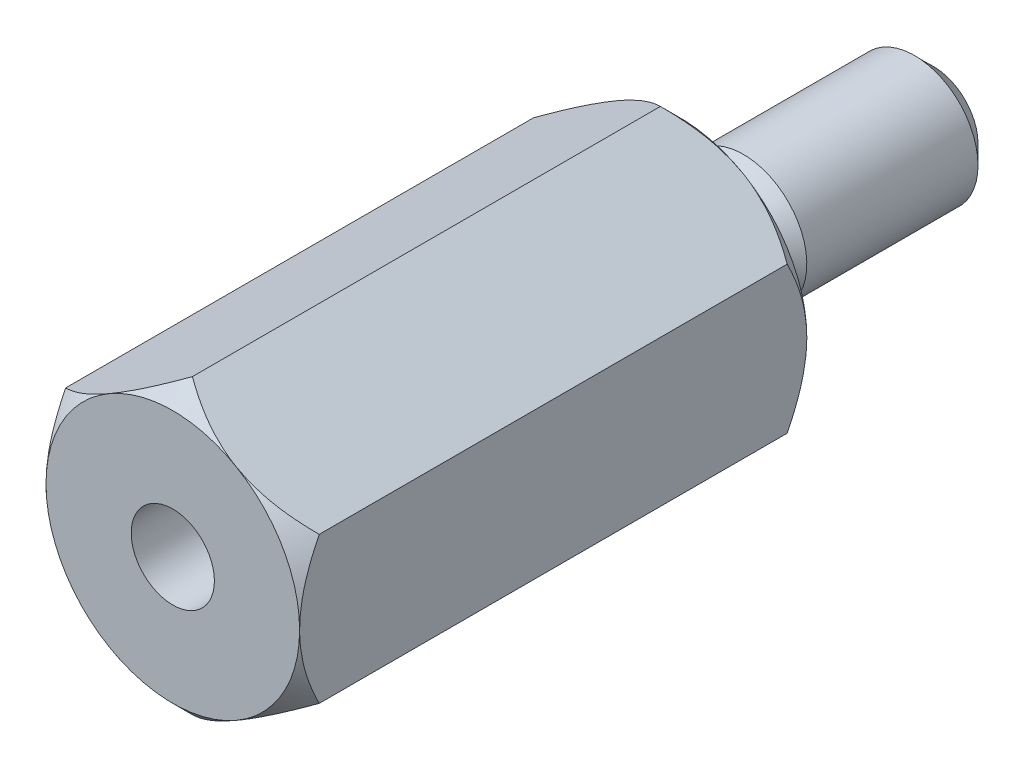
SolidWorks part; units mm, degrees
ref_plane "Front Plane" through (0, 0, 0) normal (0, 0, 1) x (1, 0, 0)
ref_plane "Top Plane" through (0, 0, 0) normal (0, 1, 0) x (1, 0, 0)
ref_plane "Right Plane" through (0, 0, 0) normal (1, 0, 0) x (0, 0, -1)
sketch "Sketch1" plane through (0, 0, 0) normal (1, 0, 0) x (0, 0, -1)
  line L0 (-19.05, 0) -> (19.05, 0) construction
  line L1 (19.05, 3.175) -> (19.05, -3.175) construction
  line L2 (-19.05, 2.0828) -> (-19.05, -2.0828) construction
  line L3 (19.05, 3.175) -> (17.78, 3.175) construction
  line L4 (-19.05, 2.0828) -> (-18.2562, 2.0828) construction
  line L5 (-19.05, -6.35) -> (-19.05, 6.35) construction
  point P0 (6.35, 0)
  point P4 (0, 0)
  point P6 (-7.9375, 0)
  point P10 (19.05, 0)
  point P12 (-19.05, 0)
  point P17 (-19.05, 0)
  dimension "Hex Length" = 25.4
  dimension "Thread Length (A)" = 12.7
  dimension "Thread Length (B)" = 11.1125
  dimension "Thread Size (B)" = 4.1656
  dimension "Thread Size (A)" = 6.35
  dimension "Pitch (B)" = 0.7937
  dimension "Pitch (A)" = 1.27
  dimension "Hex Size" = 12.7
sketch "Sketch2" plane through (0, 0, 0) normal (0, 0, 1) x (1, 0, 0)
  line L1 (6.35, 3.6662) -> (0, 7.3323)
  line L2 (0, 7.3323) -> (-6.35, 3.6662)
  line L3 (-6.35, 3.6662) -> (-6.35, -3.6662)
  line L4 (-6.35, -3.6662) -> (0, -7.3323)
  line L5 (0, -7.3323) -> (6.35, -3.6662)
  line L6 (6.35, -3.6662) -> (6.35, 3.6662)
  circle A0 centre (0, 0) radius 6.35 construction
  dimension "D1" = 12.7
extrude "Boss-Extrude1" add sketch "Sketch2" against normal blind 25.4 from vertex starting at point (0, 0, 19.05)
sketch "Sketch3" plane through (0, 0, 0) normal (1, 0, 0) x (0, 0, -1)
  line L0 (6.35, 2.2225) -> (8.5725, 2.2225)
  line L1 (6.35, -3.6662) -> (6.35, 3.6662) construction
  line L2 (8.5725, 2.2225) -> (9.525, 3.175)
  line L3 (9.525, 3.175) -> (19.05, 3.175)
  line L4 (19.05, 3.175) -> (19.05, 0)
  line L5 (19.05, 0) -> (6.35, 0)
  line L6 (6.35, 0) -> (6.35, 2.2225)
  dimension "D1" = 45
  dimension "D2" = 3.175
  dimension "D3" = 0.9525
revolve "Revolve1" add sketch "Sketch3" angle 360 about L0
chamfer "Chamfer1" distance 0.9525 angle 45 1 edges at (0, -3.175, -19.05)
sketch "Sketch4" plane through (0, 0, 19.05) normal (0, 0, 1) x (1, 0, 0)
  circle A0 centre (0, 0) radius 2.0828
extrude "Cut-Extrude1" cut sketch "Sketch4" against normal blind 11.1125
fillet "Fillet1" radius 0.0992 1 edges at (0, -2.2225, -6.35)
sketch "Sketch5" plane through (0, 0, 19.05) normal (0, 0, 1) x (1, 0, 0)
  circle A0 centre (0, 0) radius 6.35
  dimension "D1" = 12.7
extrude "Cut-Extrude2" cut sketch "Sketch5" against normal through all draft 45 flip side to cut
sketch "Sketch6" plane through (0, 0, -6.35) normal (0, 0, -1) x (-1, 0, 0)
  circle A1 centre (0, 0) radius 6.35
  circle A2 centre (0, 0) radius 6.35
  dimension "D1" = 0
extrude "Cut-Extrude3" cut sketch "Sketch6" against normal through all draft 45 flip side to cut
sketch "Sketch7" plane through (0, 0, 0) normal (1, 0, 0) x (0, 0, -1)
  line L0 (17.145, -3.175) -> (19.05, -3.175)
  line L1 (9.525, -3.175) -> (18.0975, -3.175) construction
  line L2 (-7.9375, 2.0828) -> (-19.05, 2.0828)
  line L3 (-19.05, -2.0828) -> (-7.9375, -2.0828)
  line L4 (-19.05, -2.0828) -> (-7.9375, -2.0828)
  line L5 (-7.9375, 2.0828) -> (-19.05, 2.0828)
  line L6 (-7.9375, 2.0828) -> (-7.9375, -2.0828)
  line L7 (-7.9375, 2.0828) -> (-7.9375, -2.0828)
  point P8 (17.145, -3.175)
  dimension "D1" = 1.905
sketch "Sketch8" plane through (0, 0, 19.05) normal (0, 0, 1) x (1, 0, 0)
  line L0 (0, 0) -> (0, -2.0828) construction
  line L1 (0, 0) -> (1.4728, -1.4728) construction
  circle A0 centre (0, 0) radius 2.0828 construction
  circle A1 centre (0, 0) radius 2.0828 construction
  point P6 (1.4728, -1.4728)
  dimension "D1" = 45
sketch "Sketch9" [suppressed] plane through (0, 0, 19.05) normal (0, 0, 1) x (1, 0, 0)
  circle A0 centre (0, 0) radius 2.0828 construction
  circle A1 centre (0, 0) radius 2.0828
extrude "Boss-Extrude2" [suppressed] add sketch "Sketch9" against normal up to surface (11.1125 mm away) separate body
sketch "Sketch10" [suppressed] plane through (0, 0, 19.05) normal (0, 0, 1) x (1, 0, 0)
  circle A0 centre (0, 0) radius 2.0828 construction
  circle A1 centre (0, 0) radius 2.0828
extrude "Boss-Extrude3" [suppressed] add sketch "Sketch10" against normal up to surface (11.1125 mm away)
sketch "Sketch11" [suppressed] plane through (0, 0, 19.05) normal (0, 0, 1) x (1, 0, 0)
  circle A0 centre (0, 0) radius 2.0828 construction
  circle A1 centre (0, 0) radius 2.0828
curve "Helix/Spiral1" [suppressed] pitch 0.7937 height 11.9062 turns 15
sketch "Sketch12" [suppressed] plane through (0, 0, 0) normal (1, 0, 0) x (0, 0, -1)
  line L0 (-19.05, 2.0828) -> (-19.7445, 2.0828) construction
  line L1 (-19.7445, 2.0828) -> (-19.4469, 1.5672) construction
  line L2 (-19.4469, 1.5672) -> (-19.3477, 1.5672)
  line L3 (-19.3477, 1.5672) -> (-19.05, 2.0828) construction
  line L4 (-19.3973, 2.0828) -> (-19.3973, 1.5672) construction
  line L5 (-19.5957, 1.825) -> (-19.1988, 1.825) construction
  line L6 (-20.0422, 2.5984) -> (-19.4469, 1.5672)
  line L7 (-18.7523, 2.5984) -> (-19.3477, 1.5672)
  line L8 (-20.0422, 2.5984) -> (-18.7523, 2.5984)
  point P12 (-19.7445, 2.0828)
  point P14 (-19.05, 2.0828)
  dimension "D1" = 60
  dimension "D2" = 0.0992
  dimension "D3" = 0.3969
sweep "Cut-Sweep1" [suppressed] cut profiles "Sketch12" path "Helix/Spiral1"
combine bodies "Combine1" [suppressed] operation type add bodies to combine 109 110
sketch "Sketch13" [suppressed] plane through (0, 0, 19.05) normal (0, 0, 1) x (1, 0, 0)
  circle A1 centre (0, 0) radius 2.0828
  circle A2 centre (0, 0) radius 2.0828
  dimension "D1" = 0
extrude "Cut-Extrude4" [suppressed] cut sketch "Sketch13" against normal through all draft 45
ref_plane "Plane1" [suppressed] through (0, 0, -8.5725) normal (0, 0, 1) x (1, 0, 0)
split "Split1" [suppressed] bodies to split 112
sketch "Sketch14" [suppressed] plane through (0, 0, 0) normal (1, 0, 0) x (0, 0, -1)
  line L0 (19.05, 3.175) -> (20.1612, 3.175) construction
  line L1 (20.1612, 3.175) -> (19.685, 2.3501) construction
  line L2 (19.685, 2.3501) -> (19.5262, 2.3501)
  line L3 (19.5262, 2.3501) -> (19.05, 3.175) construction
  line L4 (19.6056, 3.175) -> (19.6056, 2.3501) construction
  line L5 (19.2881, 2.7626) -> (19.9231, 2.7626) construction
  line L6 (18.5737, 3.9999) -> (19.5262, 2.3501)
  line L7 (20.6375, 3.9999) -> (19.685, 2.3501)
  line L8 (18.5737, 3.9999) -> (20.6375, 3.9999)
  point P12 (19.05, 3.175)
  point P13 (20.1612, 3.175)
  dimension "D1" = 60
  dimension "D2" = 0.1588
  dimension "D3" = 0.635
sketch "Sketch15" [suppressed] plane through (0, 0, -19.05) normal (0, 0, -1) x (-1, 0, 0)
  circle A0 centre (0, 0) radius 3.175 construction
  circle A1 centre (0, 0) radius 3.175
curve "Helix/Spiral2" [suppressed] pitch 1.27 height 13.97 turns 11
sweep "Cut-Sweep2" [suppressed] cut profiles "Sketch14" path "Helix/Spiral2"
combine bodies "Combine2" [suppressed] operation type add bodies to combine 113 115
equation "\"D1@Sketch2\"=\"Hex Size@Sketch1\""
equation "\"D1@Boss-Extrude1\"=\"Hex Length@Sketch1\""
equation "\"D2@Sketch3\"=\"Thread Length (A)@Sketch1\"*.25"
equation "\"D3@Sketch3\"=\"Pitch (A)@Sketch1\"*.75"
equation "\"D1@Chamfer1\"=\"Pitch (A)@Sketch1\"*.75"
equation "\"D1@Cut-Extrude1\"=\"Thread Length (B)@Sketch1\""
equation "\"D3@Helix/Spiral1\"=\"Thread Length (B)@Sketch1\"+\"Pitch (B)@Sketch1\""
equation "\"D4@Helix/Spiral1\"=\"Pitch (B)@Sketch1\""
equation "\"D2@Sketch12\" = \"Pitch (B)@Sketch1\" * .125"
equation "\"D3@Sketch12\" = \"Pitch (B)@Sketch1\" * .5"
equation "\"D2@Sketch14\" = \"Pitch (A)@Sketch1\" * .125"
equation "\"D3@Sketch14\" = \"Pitch (A)@Sketch1\" * .5"
equation "\"D3@Helix/Spiral2\"=\"Thread Length (A)@Sketch1\"+\"Pitch (A)@Sketch1\""
equation "\"D4@Helix/Spiral2\"=\"Pitch (A)@Sketch1\""
equation "\"D1@Sketch7\" = \"Pitch (A)@Sketch1\" * 1.5"
equation "\"D1@Sketch5\" = \"Hex Size@Sketch1\""
